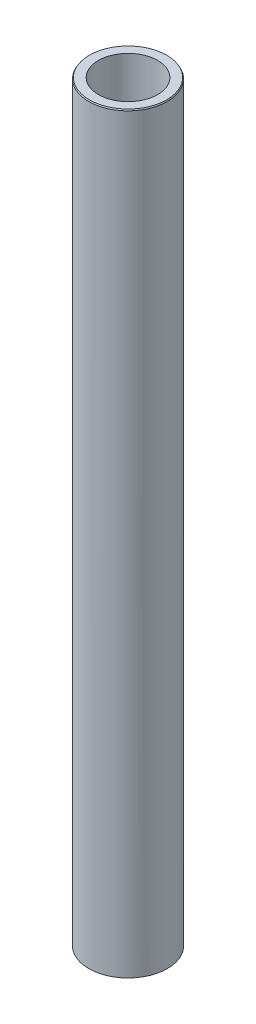
SolidWorks part; units mm, degrees
ref_plane "Front Plane" through (0, 0, 0) normal (0, 0, 1) x (1, 0, 0)
ref_plane "Top Plane" through (0, 0, 0) normal (0, 1, 0) x (1, 0, 0)
ref_plane "Right Plane" through (0, 0, 0) normal (1, 0, 0) x (0, 0, -1)
sketch "Sketch1" plane through (0, 0, 0) normal (0, 1, 0) x (1, 0, 0)
  circle A0 centre (0, 0) radius 22.5
  dimension "SHAFT_OD" = 45
extrude "Boss-Extrude1" add sketch "Sketch1" along normal blind 430.9018
sketch "Sketch2" plane through (0, 0, 0) normal (0, 1, 0) x (1, 0, 0)
  circle A0 centre (0, 0) radius 16.9495
  dimension "BORE_D" = 33.899
extrude "Cut-Extrude1" cut sketch "Sketch2" along normal through all
chamfer "Chamfer1" distance 0.6454 angle 30 2 edges at (0, 430.9018, 22.5) (0, 0, 22.5) first distance on face at (0, 430.9018, 22.5) first distance on face at (0, 0, 16.9495)
